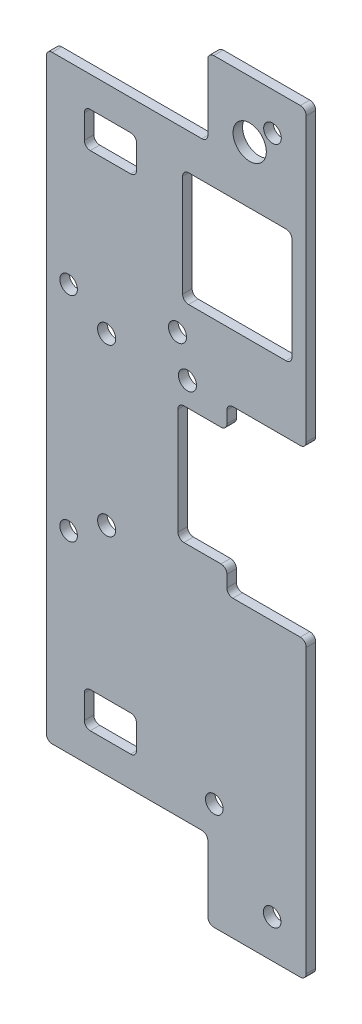
SolidWorks part; units mm, degrees
material "Thornel Mat VMA"
ref_plane "Front Plane" through (0, 0, 0) normal (0, 0, 1) x (1, 0, 0)
ref_plane "Top Plane" through (0, 0, 0) normal (0, 1, 0) x (1, 0, 0)
ref_plane "Right Plane" through (0, 0, 0) normal (1, 0, 0) x (0, 0, -1)
sketch "Sketch1" plane through (0, 0, 0) normal (0, 0, 1) x (1, 0, 0)
  line L0 (-2.9301, -104.5098) -> (-3.3149, -104.5098)
  line L1 (-3.3149, -72.8868) -> (-2.9301, -72.8868)
  line L78 (45.3299, -66.5368) -> (45.3299, -72.8868)
  line L79 (45.3299, -104.5098) -> (45.3299, -110.8598)
  line L80 (66.5174, -66.5368) -> (105.3971, 12.1397)
  line L81 (105.3971, 12.1397) -> (38.7094, 12.1397)
  line L88 (38.7094, 12.1397) -> (38.7094, -8.6883)
  line L89 (-2.9301, -8.6883) -> (38.7094, -8.6883)
  line L90 (-3.3149, -53.8368) -> (-2.9301, -53.8368)
  line L91 (-2.9301, -53.8368) -> (-2.9301, -8.6883)
  line L92 (-3.3149, -66.5368) -> (-3.3149, -53.8368)
  line L93 (-3.3149, -72.8868) -> (-3.3149, -66.5368)
  line L94 (-2.9301, -104.5098) -> (-2.9301, -72.8868)
  line L95 (-3.3149, -110.8598) -> (-3.3149, -104.5098)
  line L96 (66.5174, -110.8598) -> (105.3971, -189.5363)
  line L97 (105.3971, -189.5363) -> (38.7094, -189.5363)
  line L98 (38.7094, -189.5363) -> (38.7094, -168.7083)
  line L99 (-2.9301, -168.7083) -> (38.7094, -168.7083)
  line L106 (-3.3149, -110.8598) -> (-3.3149, -123.5598)
  line L107 (-3.3149, -123.5598) -> (-2.9301, -123.5598)
  line L108 (66.5174, -110.8598) -> (45.3299, -110.8598)
  line L109 (45.3299, -66.5368) -> (66.5174, -66.5368)
  line L110 (45.3299, -104.5098) -> (45.3299, -72.8868)
  line L111 (-2.9301, -123.5598) -> (-2.9301, -168.7083)
  circle A0 centre (90.6739, 2.6147) radius 2.3495
  circle A1 centre (41.9566, -16.4353) radius 2.3495
  circle A2 centre (3.0351, -60.1868) radius 2.3495
  circle A3 centre (3.0351, -117.2098) radius 2.3495
  circle A4 centre (41.9566, -160.9613) radius 2.3495
  circle A5 centre (90.6739, -180.0113) radius 2.3495
  circle A6 centre (51.4094, -3.1003) radius 4.445
  point P2 (90.6739, 2.6147)
  point P4 (41.9566, -16.4353)
  point P6 (3.0351, -60.1868)
  point P8 (3.0351, -117.2098)
  point P10 (41.9566, -160.9613)
  point P11 (90.6739, -180.0113)
  dimension "D2" = 4.699
  dimension "D5" = 8.89
  dimension "D1" = 66.6876
  dimension "D3" = 12.7
  dimension "D4" = 15.24
  dimension "D6" = 48.26
extrude "Boss-Extrude1" add sketch "Sketch1" along normal blind 2.54
sketch "Sketch2" plane through (0, 0, 2.54) normal (0, 0, 1) x (1, 0, 0)
  line L0 (-3.3149, -53.8368) -> (-3.3149, -72.8868) construction
  line L1 (45.3299, -66.5368) -> (66.5174, -66.5368) construction
  line L2 (45.3299, -88.6983) -> (-2.9301, -88.6983) construction
  line L3 (45.3299, -110.8598) -> (45.3299, -66.5368) construction
  line L4 (-2.9301, -72.8868) -> (-2.9301, -104.5098) construction
  circle A0 centre (13.1951, -66.5368) radius 2.413
  circle A2 centre (34.7851, -66.5368) radius 2.413
  circle A4 centre (34.7851, -110.8598) radius 2.413
  circle A6 centre (13.1951, -110.8598) radius 2.413
  dimension "D1" = 4.826
  dimension "D2" = 21.59
  dimension "D3" = 4.826
  dimension "D5" = 16.51
  dimension "D7" = 0
extrude "Cut-Extrude1" cut sketch "Sketch2" against normal through all
sketch "Sketch3" plane through (0, 0, 2.54) normal (0, 0, 1) x (1, 0, 0)
  line L0 (45.3299, -110.8598) -> (45.3299, -66.5368) construction
  line L1 (45.3299, -72.8868) -> (32.2451, -72.8868)
  line L2 (45.3299, -72.8868) -> (45.3299, -104.5098)
  line L3 (45.3299, -104.5098) -> (32.2451, -104.5098)
  line L4 (32.2451, -72.8868) -> (32.2451, -104.5098)
  line L5 (45.3299, -66.5368) -> (66.5174, -66.5368) construction
  line L6 (66.5174, -110.8598) -> (45.3299, -110.8598) construction
  circle A1 centre (13.1951, -66.5368) radius 2.413 construction
  dimension "D3" = 19.05
  dimension "D1" = 6.35
  dimension "D2" = 6.35
extrude "Cut-Extrude2" cut sketch "Sketch3" against normal through all
sketch "Sketch4" plane through (0, 0, 2.54) normal (0, 0, 1) x (1, 0, 0)
  line L0 (-2.9301, -168.7083) -> (38.7094, -168.7083) construction
  line L1 (27.4577, 15.7469) -> (40.2334, 15.7469)
  line L2 (27.4577, 15.7469) -> (27.4577, -8.6883)
  line L3 (27.4577, -8.6883) -> (40.2334, -8.6883)
  line L4 (40.2334, 15.7469) -> (40.2334, -8.6883)
  line L5 (0, -197.042) -> (40.2334, -197.042)
  line L6 (0, -197.042) -> (0, -168.7083)
  line L7 (0, -168.7083) -> (40.2334, -168.7083)
  line L8 (40.2334, -197.042) -> (40.2334, -168.7083)
  line L9 (38.7094, -168.7083) -> (38.7094, -189.5363) construction
  line L10 (38.7094, -8.6883) -> (-2.9301, -8.6883) construction
  dimension "D1" = 1.524
extrude "Cut-Extrude3" cut sketch "Sketch4" against normal through all
sketch "Sketch5" plane through (0, 0, 0) normal (0, 0, -1) x (-1, 0, 0)
  line L0 (2.9301, -8.6883) -> (2.9301, -53.8368) construction
  line L1 (-40.2334, -8.6883) -> (2.9301, -8.6883) construction
  circle A0 centre (-32.1219, -22.4043) radius 2.413
  circle A1 centre (-32.1219, -56.6943) radius 2.413
  dimension "D4" = 4.826
  dimension "D1" = 35.052
  dimension "D2" = 13.716
  dimension "D3" = 34.29
extrude "Cut-Extrude4" cut sketch "Sketch5" against normal through all
sketch "Sketch7" plane through (0, 0, 2.54) normal (0, 0, 1) x (1, 0, 0)
  line L0 (66.5174, -66.5368) -> (66.5174, 21.5221)
  line L1 (66.5174, 21.5221) -> (127.8208, 21.5221)
  line L2 (66.5174, -110.8598) -> (66.5174, -200.2563)
  line L3 (66.5174, -200.2563) -> (115.7822, -200.2563)
  line L4 (115.7822, -200.2563) -> (127.8208, 21.5221)
  line L5 (66.5174, -66.5368) -> (66.5174, -110.8598)
extrude "Cut-Extrude5" cut sketch "Sketch7" against normal through all both and the other way through all
extrude "Cut-Extrude6" cut sketch "Sketch8" against normal through all
sketch "Sketch8" plane through (-2.1864, -156.0179, 0) normal (0, 0, -1) x (0.9999, -0.0134, 0)
  circle A0 centre (57.5716, -158.8222) radius 2.3495
  circle A1 centre (59.8998, 22.5177) radius 2.3495
fillet "Fillet1" radius 1.5875 16 edges at (-2.9301, -168.7083, 1.27) (40.2334, -168.7083, 1.27) (40.2334, -189.5363, 1.27) (66.5174, -189.5363, 1.27) (66.5174, -110.8598, 1.27) (45.3299, -110.8598, 1.27) (45.3299, -104.5098, 1.27) (32.2451, -104.5098, 1.27) (32.2451, -72.8868, 1.27) (45.3299, -72.8868, 1.27) (45.3299, -66.5368, 1.27) (66.5174, -66.5368, 1.27) (66.5174, 12.1397, 1.27) (40.2334, 12.1397, 1.27) (40.2334, -8.6883, 1.27) (-2.9301, -8.6883, 1.27)
sketch "Sketch9" plane through (0, -123.5598, 0) normal (0, -1, 0) x (1, 0, 0)
  line L1 (-3.3149, 2.54) -> (-2.9301, 2.54)
  line L2 (-3.3149, 2.54) -> (-3.3149, 0)
  line L3 (-3.3149, 0) -> (-2.9301, 0)
  line L4 (-2.9301, 2.54) -> (-2.9301, 0)
extrude "Cut-Extrude7" cut sketch "Sketch9" against normal through all
sketch "Sketch10" plane through (0, 0, 0) normal (0, 0, -1) x (-1, 0, 0)
  line L0 (-40.2334, -7.1008) -> (-40.2334, 10.5522) construction
  line L1 (-33.4974, -18.3403) -> (-62.7074, -18.3403)
  line L2 (-33.4974, -18.3403) -> (-33.4974, -48.8203)
  line L3 (-33.4974, -48.8203) -> (-62.7074, -48.8203)
  line L4 (-62.7074, -18.3403) -> (-62.7074, -48.8203)
  line L6 (-38.6459, -8.6883) -> (1.3426, -8.6883) construction
  line L7 (2.9301, -10.2758) -> (2.9301, -167.1208) construction
  line L8 (-7.2299, -16.8163) -> (-21.1999, -16.8163)
  line L9 (-7.2299, -16.8163) -> (-7.2299, -26.3413)
  line L10 (-7.2299, -26.3413) -> (-21.1999, -26.3413)
  line L11 (-21.1999, -16.8163) -> (-21.1999, -26.3413)
  line L12 (-32.2451, -88.6983) -> (2.9301, -88.6983) construction
  line L13 (-32.2451, -74.4743) -> (-32.2451, -102.9223) construction
  line L14 (-21.1999, -160.5803) -> (-21.1999, -151.0553)
  line L15 (-7.2299, -151.0553) -> (-21.1999, -151.0553)
  line L16 (-7.2299, -160.5803) -> (-7.2299, -151.0553)
  line L17 (-7.2299, -160.5803) -> (-21.1999, -160.5803)
  line L18 (-64.9299, 12.1397) -> (-41.8209, 12.1397) construction
  line L19 (-66.5174, 10.5522) -> (-66.5174, -64.9493) construction
  dimension "D1" = 30.48
  dimension "D2" = 29.21
  dimension "D3" = 8.128
  dimension "D4" = 9.525
  dimension "D5" = 10.16
  dimension "D6" = 13.97
  dimension "D7" = 30.48
  dimension "D8" = 3.81
extrude "Cut-Extrude8" cut sketch "Sketch10" against normal blind 2.54
sketch "Sketch12" plane through (0, 0, 0) normal (0, 0, -1) x (-1, 0, 0)
  line L0 (-46.5451, -18.3403) -> (-33.4974, -18.3403)
  line L1 (-43.3317, -18.3403) -> (-62.7074, -18.3403) construction
  line L2 (-33.4974, -18.3403) -> (-33.4974, -26.6795)
  line L3 (-33.4974, -48.8203) -> (-33.4974, -24.3869) construction
  line L4 (-33.4974, -26.6795) -> (-21.1999, -26.6795)
  line L5 (-21.1999, -16.8163) -> (-21.1999, -26.3413) construction
  line L6 (-21.1999, -26.6795) -> (-21.1999, -16.8163)
  line L7 (-21.1999, -16.8163) -> (-46.5451, -12.5328)
  line L8 (-46.5451, -12.5328) -> (-46.5451, -18.3403)
  line L9 (-33.8326, -104.5098) -> (-43.7424, -104.5098) construction
  line L10 (-40.1395, -107.4088) -> (-27.7341, -107.4088)
  line L11 (-40.1395, -107.4088) -> (-40.1395, -114.3781)
  line L12 (-40.1395, -114.3781) -> (-27.7341, -114.3781)
  line L13 (-27.7341, -107.4088) -> (-27.7341, -114.3781)
  line L14 (-45.3299, -109.2723) -> (-45.3299, -106.0973) construction
  dimension "D1" = 5.8075
  dimension "D2" = 8.3393
  dimension "D3" = 25.3451
  dimension "D4" = 12.4054
  dimension "D5" = 6.9693
  dimension "D6" = 2.899
  dimension "D7" = 5.1904
extrude "Boss-Extrude2" add sketch "Sketch12" against normal up to surface (2.54 mm away) up to face at (14.2149, -21.5788, 2.54)
fillet "Fillet2" radius 1.5875 12 edges at (21.1999, -160.5803, 1.27) (21.1999, -151.0553, 1.27) (7.2299, -151.0553, 1.27) (7.2299, -160.5803, 1.27) (21.1999, -26.3413, 1.27) (21.1999, -16.8163, 1.27) (7.2299, -16.8163, 1.27) (7.2299, -26.3413, 1.27) (33.4974, -48.8203, 1.27) (33.4974, -18.3403, 1.27) (62.7074, -48.8203, 1.27) (62.7074, -18.3403, 1.27)
